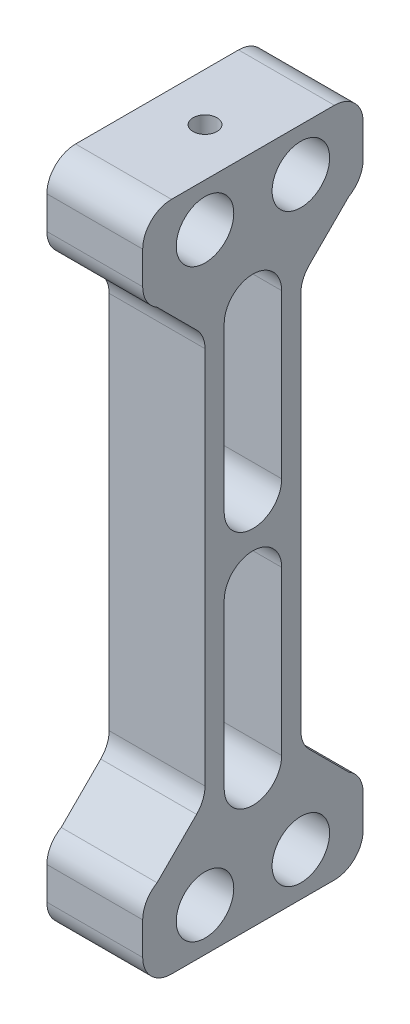
SolidWorks part; units mm, degrees
material "7050-T73510"
ref_plane "Front Plane" through (0, 0, 0) normal (0, 0, 1) x (1, 0, 0)
ref_plane "Top Plane" through (0, 0, 0) normal (0, 1, 0) x (1, 0, 0)
ref_plane "Right Plane" through (0, 0, 0) normal (1, 0, 0) x (0, 0, -1)
sketch "Sketch1" plane through (0, 0, 0) normal (1, 0, 0) x (0, 0, -1)
  line L0 (-10, 4.5) -> (0, 4.5)
  line L1 (-10, -4.5) -> (0, -4.5)
  line L2 (0, 4.5) -> (0, 56.5)
  line L3 (0, 30.5) -> (-10, 30.5)
  line L4 (-10, 56.5) -> (-10, 4.5)
  line L5 (0, 30.5) -> (-21.5774, 30.5) construction
  line L6 (-10, 65.5) -> (0, 65.5)
  line L7 (-10, 56.5) -> (0, 56.5)
  line L8 (-5, 65.5) -> (-5, -4.5) construction
  line L9 (-5, 51.5) -> (-5, 34.5) construction
  line L10 (-2, 51.5) -> (-2, 34.5)
  line L11 (-8, 51.5) -> (-8, 34.5)
  line L12 (-5, 26.5) -> (-5, 9.5) construction
  line L13 (-2, 26.5) -> (-2, 9.5)
  line L14 (-8, 26.5) -> (-8, 9.5)
  line L15 (0, 4.5) -> (2, 4.5)
  line L16 (2, 4.5) -> (2, -4.5)
  line L17 (2, -4.5) -> (0, -4.5)
  line L18 (-10, 4.5) -> (-12, 4.5)
  line L19 (-12, -4.5) -> (-10, -4.5)
  line L20 (2, 65.5) -> (0, 65.5)
  line L21 (0, 56.5) -> (2, 56.5)
  line L22 (-10, 56.5) -> (-12, 56.5)
  line L23 (-12, 65.5) -> (-10, 65.5)
  line L24 (-16.5, 61) -> (-16.5, 65.5)
  line L25 (-16.5, 65.5) -> (-12, 65.5)
  line L26 (-16.5, 61) -> (-16.5, 56.5)
  line L27 (-16.5, 56.5) -> (-12, 56.5)
  line L28 (6.5, 56.5) -> (2, 56.5)
  line L29 (6.5, 61) -> (6.5, 56.5)
  line L30 (6.5, 61) -> (6.5, 65.5)
  line L31 (6.5, 65.5) -> (2, 65.5)
  line L32 (-12, 4.5) -> (-16.5, 4.5)
  line L33 (-16.5, 4.5) -> (-16.5, 0)
  line L34 (-16.5, 0) -> (-16.5, -4.5)
  line L35 (-16.5, -4.5) -> (-12, -4.5)
  line L36 (2, 4.5) -> (6.5, 4.5)
  line L37 (6.5, 4.5) -> (6.5, 0)
  line L38 (6.5, 0) -> (6.5, -4.5)
  line L39 (6.5, -4.5) -> (2, -4.5)
  circle A0 centre (0, 0) radius 4.5
  circle A1 centre (-10, 0) radius 4.5
  circle A2 centre (-10, 0) radius 3
  circle A3 centre (0, 0) radius 3
  circle A4 centre (0, 61) radius 3
  circle A5 centre (-10, 61) radius 3
  circle A6 centre (-10, 61) radius 4.5
  circle A7 centre (0, 61) radius 4.5
  arc A8 (-2, 51.5) -> (-8, 51.5) centre (-5, 51.5) ccw
  arc A9 (-8, 34.5) -> (-2, 34.5) centre (-5, 34.5) ccw
  arc A10 (-2, 26.5) -> (-8, 26.5) centre (-5, 26.5) ccw
  arc A11 (-8, 9.5) -> (-2, 9.5) centre (-5, 9.5) ccw
  circle A12 centre (2, 0) radius 4.5
  circle A13 centre (-12, 0) radius 4.5
  circle A14 centre (2, 61) radius 4.5
  circle A15 centre (-12, 61) radius 4.5
  point P28 (-5, 43)
  point P33 (-5, 18)
  dimension "D1" = 9
  dimension "D3" = 6
  dimension "D4" = 6
  dimension "D7" = 3
  dimension "D8" = 3
  dimension "D5" = 10
  dimension "D6" = 61
  dimension "D9" = 17
  dimension "D10" = 17
  dimension "D11" = 4
  dimension "D12" = 4
  dimension "D13" = 2
extrude "Boss-Extrude1" add sketch "Sketch1" along normal blind 10 contours A15 L25 L24 | A6 A15 | A15 A5 A6 | A15 L26 L27 | L7 A7 L6 A6 | A14 A7 A4 | A14 A7 | L29 A14 L28 | L31 A14 L30 | A7 A14 A4 | L7 L4 L3 L2 A9 L11 A8 L10 | L3 L4 L0 L2 A11 L14 A10 L13 | A1 L1 A0 L0 | A12 A0 A3 | A0 A12 A3 L16 | A3 L16 A0 | A3 A12 A0 L16 | A12 L16 A0 | A12 A0 L17 | A0 A12 L16 | A12 L39 L38 | A12 L37 L36 | A12 L15 A0 | L16 A12 A0 | A13 A1 | L33 A13 L32 | L18 A13 A1 | A2 A13 A1 | A13 A2 A1 | L35 A13 L34 | A1 A13 L19 | A5 A15 A6 | A15 L22 A6 | A15 A6 L23 | A7 A14 L20 | L21 A14 A7
chamfer "Chamfer1" distance 5 angle 45 4 edges at (5, 56.5, 10) (5, 56.5, 0) (5, 4.5, 0) (5, 4.5, 10)
fillet "Fillet1" radius 3 12 edges at (5, 51.5, 0) (5, 9.5, 0) (5, 9.5, 10) (5, 51.5, 10) (5, 56.5, 16.5) (5, 65.5, 16.5) (5, 65.5, -6.5) (5, 56.5, -6.5) (5, 4.5, -6.5) (5, -4.5, -6.5) (5, -4.5, 16.5) (5, 4.5, 16.5)
sketch "Sketch4" plane through (10, 0, 0) normal (1, 0, 0) x (0, 0, -1)
  line L0 (-8.5, 65.5) -> (-8.5, 61)
  line L1 (-13.5, 65.5) -> (3.5, 65.5) construction
  line L2 (-8.5, 61) -> (-16.5, 60.799)
  line L3 (-16.5, 59.0981) -> (-16.5, 62.5) construction
  line L4 (-16.5, 60.799) -> (-16.5, 65.5)
  line L5 (-16.5, 65.5) -> (-8.5, 65.5)
  line L6 (-5, 65.5) -> (-5, 54.5) construction
  line L7 (-10, 30.5) -> (0, 30.5) construction
  line L8 (-10, 50.2574) -> (-10, 10.7426) construction
  line L9 (0, 10.7426) -> (0, 50.2574) construction
  line L10 (6.5, 65.5) -> (-1.5, 65.5)
  line L11 (6.5, 60.799) -> (6.5, 65.5)
  line L12 (-1.5, 61) -> (6.5, 60.799)
  line L13 (-1.5, 65.5) -> (-1.5, 61)
  line L14 (-1.5, -4.5) -> (-1.5, 0)
  line L15 (-1.5, 0) -> (6.5, 0.201)
  line L16 (6.5, 0.201) -> (6.5, -4.5)
  line L17 (6.5, -4.5) -> (-1.5, -4.5)
  line L18 (-16.5, -4.5) -> (-8.5, -4.5)
  line L19 (-16.5, 0.201) -> (-16.5, -4.5)
  line L20 (-8.5, 0) -> (-16.5, 0.201)
  line L21 (-8.5, -4.5) -> (-8.5, 0)
  arc A0 (-2, 51.5) -> (-8, 51.5) centre (-5, 51.5) ccw construction
  dimension "D1" = 8
  dimension "D2" = 4.5
extrude "Cut-Extrude1" [suppressed] cut sketch "Sketch4" against normal blind 10
fillet "Fillet2" [suppressed] radius 1.5
hole_wizard "M3 Tapped Hole1" [suppressed] positions "Sketch6" profile "Sketch5" tap size "M3" standard "ISO"
sketch "Sketch6" [suppressed] plane through (0, 61.1749, 1.5367) normal (0, 0.9997, 0.0251) x (1, 0, 0)
  line L3 (10, -14.968) -> (10, -11.4648) construction
  line L4 (0, -6.8525) -> (10, -6.8525) construction
  line L5 (0, 0.1453) -> (10, 0.1453) construction
  point P0 (5, -10.3525)
  point P2 (5, 3.6453)
  dimension "D1" = 5
  dimension "D2" = 3.5
  dimension "D3" = 3.5
sketch "Sketch5" plane through (5, 60.9149, 11.8859) normal (1, 0, 0) x (0, -0.0251, 0.9997)
  line L0 (0, 0) -> (0, 18.2511)
  line L1 (0, 18.2511) -> (1.25, 17.5)
  line L2 (1.25, 17.5) -> (1.25, 0)
  line L5 (1.25, 0) -> (0, 0)
  line L10 (0, 18.2511) -> (-1.25, 17.5) construction
  line L11 (0, -6.35) -> (0, 107.95) construction
  dimension "Tap Drill Dia." = 2.5
  dimension "Tap Drill Depth" = 17.5
  dimension "Drill Angle" = 118
cosmetic thread "Hole Thread1"
cosmetic thread "Hole Thread2"
hole_wizard "M3 Tapped Hole2" [suppressed] positions "Sketch8" profile "Sketch7" tap size "M3" standard "ISO"
sketch "Sketch8" [suppressed] plane through (0, 65.5, 0) normal (0, 1, 0) x (1, 0, 0)
  line L0 (0, -8.5) -> (10, -8.5) construction
  line L1 (5, -8.5) -> (5, -1.5) construction
  line L2 (0, -1.5) -> (10, -1.5) construction
  point P0 (5, -5)
sketch "Sketch7" plane through (5, 65.5, 5) normal (1, 0, 0) x (0, 0, 1)
  line L0 (0, 0) -> (0, 8.2511)
  line L1 (0, 8.2511) -> (1.25, 7.5)
  line L2 (1.25, 7.5) -> (1.25, 0)
  line L5 (1.25, 0) -> (0, 0)
  line L10 (0, 8.2511) -> (-1.25, 7.5) construction
  line L11 (0, -6.35) -> (0, 107.95) construction
  dimension "Tap Drill Dia." = 2.5
  dimension "Tap Drill Depth" = 7.5
  dimension "Drill Angle" = 118
cosmetic thread "Hole Thread3"
hole_wizard "M3 Tapped Hole3" positions "3DSketch1" profile "Sketch11" tap size "M3" standard "ISO"
sketch3d "3DSketch1"
  line L0 (10, -4.5, 13.5) -> (10, -4.5, -3.5) construction
  line L1 (0, 65.5, 13.5) -> (0, 65.5, -3.5) construction
  point P0 (5, 65.5, 5)
  point P2 (5, -4.5, 5)
  dimension "D1" = 5
  dimension "D2" = 5
  dimension "D3" = 11.5
  dimension "D4" = 11.5
sketch "Sketch11" plane through (5, 65.5, 5) normal (1, 0, 0) x (0, 0, 1)
  line L0 (0, 0) -> (0, 8.2511)
  line L1 (0, 8.2511) -> (1.25, 7.5)
  line L2 (1.25, 7.5) -> (1.25, 0)
  line L5 (1.25, 0) -> (0, 0)
  line L10 (0, 8.2511) -> (-1.25, 7.5) construction
  line L11 (0, -6.35) -> (0, 107.95) construction
  dimension "Tap Drill Dia." = 2.5
  dimension "Tap Drill Depth" = 7.5
  dimension "Drill Angle" = 118
cosmetic thread "Hole Thread4"
cosmetic thread "Hole Thread5"
